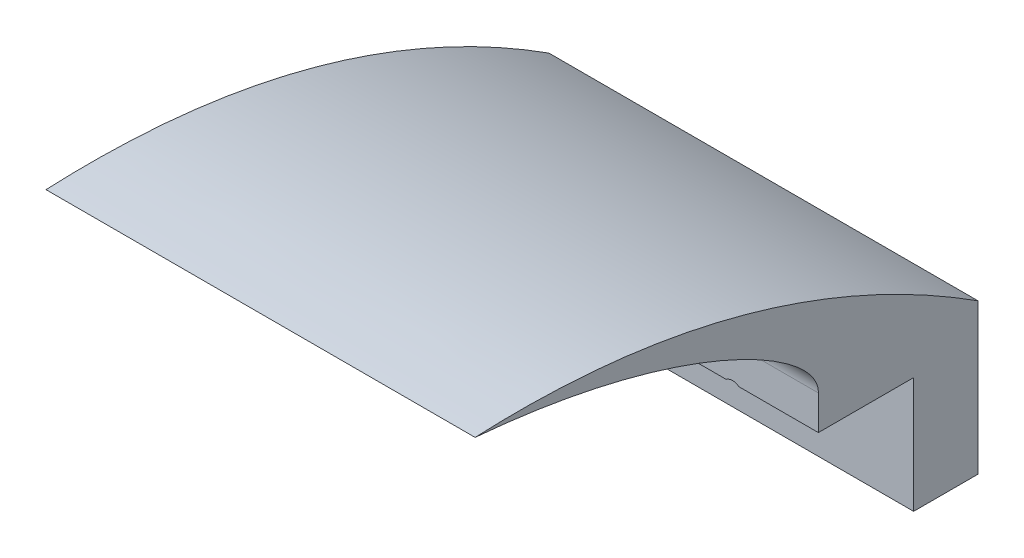
SolidWorks part; units mm, degrees
material "ABS"
ref_plane "Front Plane" through (0, 0, 0) normal (0, 0, 1) x (1, 0, 0)
ref_plane "Top Plane" through (0, 0, 0) normal (0, 1, 0) x (1, 0, 0)
ref_plane "Right Plane" through (0, 0, 0) normal (1, 0, 0) x (0, 0, -1)
curve "Curve1"
  spline degree 3 poles (0, 0.0012, 1.0003) (0, 0.0015, 0.9994) (0, 0.0028, 0.9958) (0, 0.0055, 0.9879) (0, 0.0099, 0.9747) (0, 0.0159, 0.9565) (0, 0.0233, 0.9333) (0, 0.0318, 0.9054) (0, 0.0411, 0.8731) (0, 0.051, 0.8366) (0, 0.0612, 0.7964) (0, 0.0713, 0.7528) (0, 0.0811, 0.7063) (0, 0.0903, 0.6574) (0, 0.0985, 0.6067) (0, 0.1057, 0.5546) (0, 0.1115, 0.5018) (0, 0.1158, 0.4488) (0, 0.1186, 0.3959) (0, 0.1189, 0.3436) (0, 0.1164, 0.2927) (0, 0.1112, 0.2442) (0, 0.1037, 0.1988) (0, 0.0942, 0.157) (0, 0.0831, 0.1194) (0, 0.0711, 0.0865) (0, 0.0584, 0.0585) (0, 0.0457, 0.0357) (0, 0.0334, 0.0184) (0, 0.0218, 0.0064) (0, 0.0108, -0.0005) (0, -0.0003, -0.0011) (0, -0.0092, 0.0055) (0, -0.0148, 0.017) (0, -0.0185, 0.0329) (0, -0.0204, 0.0533) (0, -0.0208, 0.0781) (0, -0.0198, 0.107) (0, -0.0176, 0.1398) (0, -0.0147, 0.176) (0, -0.0111, 0.2153) (0, -0.0074, 0.2574) (0, -0.0037, 0.3019) (0, -0.0005, 0.3484) (0, 0.002, 0.397) (0, 0.0037, 0.4471) (0, 0.0055, 0.4983) (0, 0.0069, 0.5496) (0, 0.0079, 0.6006) (0, 0.0085, 0.6505) (0, 0.0086, 0.699) (0, 0.0083, 0.7455) (0, 0.0076, 0.7894) (0, 0.0065, 0.8302) (0, 0.0053, 0.8675) (0, 0.0039, 0.9007) (0, 0.0027, 0.9296) (0, 0.0013, 0.9539) (0, 0.0006, 0.9727) (0, -0.0011, 0.9872) (0, 0, 0.9944) (0, -0.002, 0.9999) (0, -0.0005, 1) (0, 0, 1) knots 0 0 0 0 0.001372 0.005465 0.012235 0.021602 0.033461 0.047671 0.064081 0.082496 0.102719 0.124527 0.147676 0.171913 0.196978 0.222597 0.248497 0.274385 0.300041 0.32569 0.350525 0.37428 0.396711 0.417577 0.436654 0.453744 0.46868 0.481329 0.491631 0.499616 0.505546 0.510185 0.514824 0.520702 0.528516 0.538466 0.550543 0.564643 0.580638 0.598345 0.617584 0.638174 0.659922 0.682632 0.706121 0.730727 0.7557 0.780732 0.805564 0.829932 0.85357 0.876213 0.89761 0.917519 0.935698 0.951943 0.966047 0.97784 0.987174 0.993932 0.998018 0.999386 1 1 1 1
sketch "Sketch1" plane through (0, 0, 0) normal (1, 0, 0) x (0, 0, -1)
  line L1 (0.8093, 1.5275) -> (0.8093, -8.6325)
  line L3 (48.0533, 1.5275) -> (48.0533, -42.9225)
  line L4 (48.0533, -42.9225) -> (29.0033, -42.9225)
  line L5 (29.0033, -42.9225) -> (29.0033, -8.6325)
  line L6 (29.0033, -8.6325) -> (0.8093, -8.6325)
  line L8 (0.5507, 0) -> (-0.5507, 0) construction
  line L10 (0, 0.0768) -> (0, -0.0768) construction
  spline S0 degree 2 poles (-100.7907, 40.9362) (-19.4323, 44.7232) (48.0533, 1.5275) knots 0 0 0 1 1 1
  spline S1 degree 3 poles (-100.7907, 40.9362) (-95.812, 40.5065) (-85.4041, 39.3561) (-70.047, 36.8254) (-55.2045, 33.4552) (-41.8487, 29.54) (-30.1359, 25.2555) (-20.1921, 20.775) (-12.1117, 16.2715) (-5.9305, 11.9042) (-1.6817, 7.7681) (0.4919, 4.2872) (0.8118, 2.163) (0.8093, 1.5275) knots 0.353791 0.353791 0.353791 0.353791 0.37428 0.396711 0.417577 0.436654 0.453744 0.46868 0.481329 0.491631 0.499616 0.505546 0.508115 0.508115 0.508115 0.508115
  dimension "D2" = 1.5275
  dimension "D3" = 10.16
  dimension "D5" = 100.7907
  dimension "D6" = 47.244
  dimension "D7" = 44.45
  dimension "D8" = 34.29
  dimension "D9" = 19.05
  dimension "D10" = 29.1024
  dimension "D11" = 9.7768
  dimension "D12" = 48.0533
  dimension "D14" = 40.9362
extrude "Boss-Extrude1" add sketch "Sketch1" along normal mid plane 127
sketch "Sketch2" plane through (0, 0, -48.0533) normal (0, 0, -1) x (-1, 0, 0)
  line L0 (-63.5, -11.1725) -> (-38.1, -11.1725) construction
  line L1 (-63.5, -42.9225) -> (-63.5, 1.5275) construction
  line L2 (-38.1, -11.1725) -> (38.1, -11.1725) construction
  line L3 (38.1, -11.1725) -> (63.5, -11.1725) construction
  line L4 (63.5, -42.9225) -> (63.5, 1.5275) construction
  line L5 (-63.5, 1.5275) -> (63.5, 1.5275) construction
  circle A0 centre (-38.1, -11.1725) radius 3.175
  circle A1 centre (38.1, -11.1725) radius 3.175
  dimension "D1" = 6.35
  dimension "D2" = 25.4
  dimension "D3" = 12.7
extrude "Cut-Extrude1" cut sketch "Sketch2" against normal through all both and the other way through all
